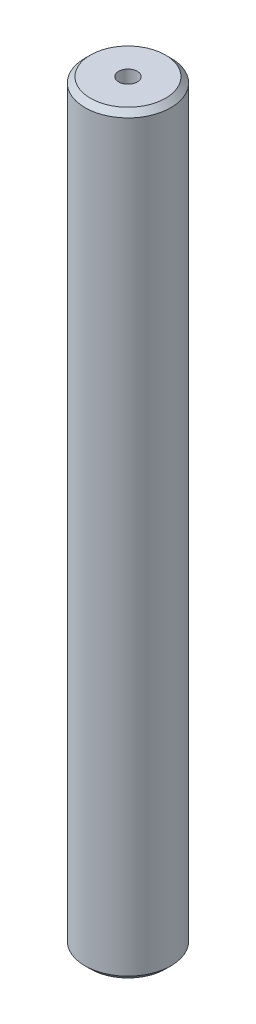
SolidWorks part; units mm, degrees
ref_plane "Front Plane" through (0, 0, 0) normal (0, 0, 1) x (1, 0, 0)
ref_plane "Top Plane" through (0, 0, 0) normal (0, 1, 0) x (1, 0, 0)
ref_plane "Right Plane" through (0, 0, 0) normal (1, 0, 0) x (0, 0, -1)
sketch "Sketch1" plane through (0, 0, 0) normal (0, 1, 0) x (1, 0, 0)
  circle A0 centre (0, 0) radius 5
  dimension "SHAFT_OD" = 10
extrude "Boss-Extrude1" add sketch "Sketch1" along normal blind 87.8104
sketch "Sketch2" plane through (0, 0, 0) normal (0, 1, 0) x (1, 0, 0)
  circle A0 centre (0, 0) radius 1.0848
  dimension "BORE_D" = 2.1696
extrude "Cut-Extrude1" cut sketch "Sketch2" along normal through all
chamfer "Chamfer1" distance 0.6318 angle 45 2 edges at (0, 87.8104, 5) (0, 0, 5)
